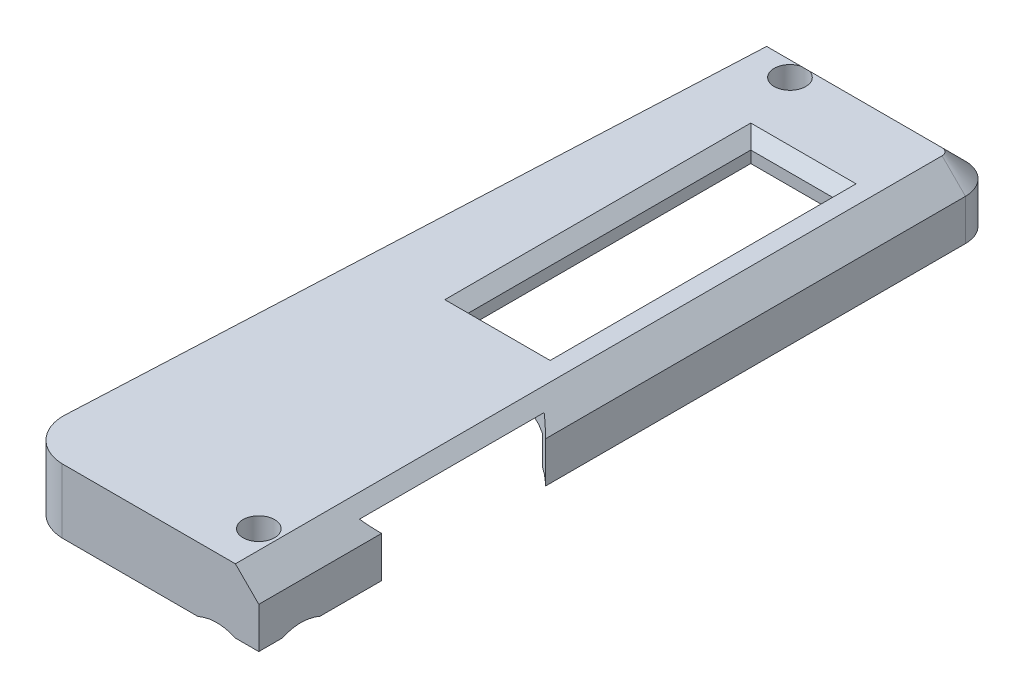
SolidWorks part; units mm, degrees
ref_plane "前视基准面" through (0, 0, 0) normal (0, 0, 1) x (1, 0, 0)
ref_plane "上视基准面" through (0, 0, 0) normal (0, 1, 0) x (1, 0, 0)
ref_plane "右视基准面" through (0, 0, 0) normal (1, 0, 0) x (0, 0, -1)
other "Configuration Table"
sketch "草图1" plane through (0, 0, 0) normal (0, 1, 0) x (1, 0, 0)
  line L0 (0, 3.3) -> (11.7, 3.3)
  line L1 (14.3, 0.7) -> (14.3, -59.7)
  line L2 (14.3, -59.7) -> (-3.3, -59.7)
  line L3 (-3.3, -59.7) -> (-3.3, 0)
  line L4 (-3.3, 0) -> (-3.3, 3.3)
  line L5 (-3.3, 3.3) -> (0, 3.3)
  circle A0 centre (0, 0) radius 1.35
  circle A1 centre (0, 0) radius 3.3 construction
  arc A2 (14.3, 0.7) -> (11.7, 3.3) centre (11.7, 0.7) ccw
  circle A3 centre (10.7, -56.1) radius 1.35
  dimension "D1" = 2.7
  dimension "D2" = 6.6
  dimension "D3" = 14.3
  dimension "D4" = 2.6
  dimension "D6" = 10.7
  dimension "D7" = 56.1
  dimension "D5" = 63
extrude "凸台-拉伸1" add sketch "草图1" along normal blind 2
sketch "草图2" plane through (0, 2, 0) normal (0, 1, 0) x (1, 0, 0)
  line L0 (-3.3, 1.1799) -> (-6.1716, -59.7)
  line L1 (-3.3, 1.1799) -> (-3.3, -59.7)
  line L2 (-6.0014, -56.0919) -> (-3.2, 3.3) construction
  line L4 (-3.3, -59.7) -> (-6.1716, -59.7)
  line L7 (-3.3, 3.3) -> (-3.3, -59.7) construction
extrude "凸台-拉伸2" add sketch "草图2" against normal up to surface (2 mm away) up to face at (6.8477, 0, 22.3123)
sketch "草图3" plane through (0, 2, 0) normal (0, 1, 0) x (1, 0, 0)
  line L0 (-3.3, 1.1799) -> (-3.2, 3.3)
  line L1 (11.7, 3.3) -> (-3.3, 3.3) construction
  line L2 (-3.2, 3.3) -> (-3.3, 3.3)
  line L3 (-3.3, 3.3) -> (-3.3, 1.1799)
  line L4 (-3.3, 1.1799) -> (-6.1716, -59.7) construction
  line L5 (-2.3, -59.7) -> (-6.1716, -59.7)
  line L6 (-6.1716, -59.7) -> (-6.0014, -56.0919)
  arc A0 (-6.0014, -56.0919) -> (-2.3, -59.7) centre (-2.4, -56.1) ccw construction
  arc A1 (-6.0014, -56.0919) -> (-2.3, -59.7) centre (-2.4, -56.1) ccw
  line M3 (11.7, 3.3) -> (-3.3, 3.3)
  line M4 (-3.3, 3.3) -> (-3.3, 1.1799)
  line M5 (-3.3, 1.1799) -> (-6.1716, -59.7)
  line M6 (-6.1716, -59.7) -> (14.3, -59.7)
extrude "切除-拉伸1" cut sketch "草图3" against normal through all and the other way through all contours L0 M4 M3 | A1 M5 M6
sketch "草图4" plane through (0, 0, 0) normal (0, -1, 0) x (1, 0, 0)
  line L21 (12.8, -0.7) -> (12.8, 58.2)
  line L22 (12.8, 58.2) -> (-2.4764, 58.2)
  line L23 (-4.5013, 56.1245) -> (-1.7691, -1.8)
  line L24 (-1.7691, -1.8) -> (11.7, -1.8)
  line L25 (12.8, -0.7) -> (12.8, 54.3245)
  line L26 (8.9245, 58.2) -> (-2.4764, 58.2)
  line L27 (-4.5013, 56.1245) -> (-1.9457, 1.9434)
  line L28 (2.0791, -1.8) -> (11.7, -1.8)
  line L33 (-6.0014, 56.0919) -> (-3.2, -3.3)
  line L34 (-3.2, -3.3) -> (11.7, -3.3)
  line L35 (14.3, -0.7) -> (14.3, 59.7)
  line L36 (14.3, 59.7) -> (-2.5, 59.7)
  line L37 (-6.0014, 56.0919) -> (-3.2, -3.3)
  line L38 (-3.2, -3.3) -> (11.7, -3.3)
  line L39 (14.3, -0.7) -> (14.3, 59.7)
  line L40 (14.3, 59.7) -> (-2.5, 59.7)
  arc A7 (11.7, -1.8) -> (12.8, -0.7) centre (11.7, -0.7) ccw
  arc A8 (-2.4764, 58.2) -> (-4.5013, 56.1245) centre (-2.4, 56.1) ccw
  arc A9 (11.7, -1.8) -> (12.8, -0.7) centre (11.7, -0.7) ccw
  arc A10 (-2.4764, 58.2) -> (-4.5013, 56.1245) centre (-2.4, 56.1) ccw
  arc A13 (11.7, -3.3) -> (14.3, -0.7) centre (11.7, -0.7) ccw
  arc A14 (-2.5, 59.7) -> (-6.0014, 56.0919) centre (-2.4, 56.1) ccw
  arc A15 (11.7, -3.3) -> (14.3, -0.7) centre (11.7, -0.7) ccw
  arc A16 (-2.5, 59.7) -> (-6.0014, 56.0919) centre (-2.4, 56.1) ccw
  circle A21 centre (10.7, 56.1) radius 2.75
  arc A22 (12.8, 54.3245) -> (8.9245, 58.2) centre (10.7, 56.1) ccw
  circle A24 centre (0, 0) radius 2.75
  arc A25 (-1.9457, 1.9434) -> (2.0791, -1.8) centre (0, 0) ccw
  dimension "D1" = 1.5
  dimension "D2" = 0
  dimension "D3" = 0.5
  dimension "D4" = 0.5
extrude "凸台-拉伸3" add sketch "草图4" along normal up to surface (3.5 mm away)
sketch "草图5" plane through (14.3, 0, 0) normal (1, 0, 0) x (0, 0, -1)
  line L0 (-59.7, -3.5) -> (0.7, -3.5) construction
  line L1 (-35.2, -3.5) -> (-49.2, -3.5)
  line L2 (-35.2, -3.5) -> (-35.2, 1)
  line L3 (-35.2, 1) -> (-49.2, 1)
  line L4 (-49.2, -3.5) -> (-49.2, 1)
  line L5 (-35.2, -3.5) -> (-49.2, 1) construction
  line L6 (-35.2, 1) -> (-49.2, -3.5) construction
  line L7 (-42.2, 0.55) -> (-42.2, -3.5) construction
  line L8 (-34.0108, 0.55) -> (-50.3892, 0.55) construction
  point P4 (-42.2, -1.25)
  dimension "D1" = 14
  dimension "D2" = 4.5
extrude "切除-拉伸2" cut sketch "草图5" against normal blind 9
sketch "草图6" plane through (0, -3.5, 0) normal (0, -1, 0) x (1, 0, 0)
  line L0 (2.1586, 33.5397) -> (2.1586, 50.8603)
  arc A0 (2.1586, 33.5397) -> (2.1586, 50.8603) centre (7.1586, 42.2) ccw
  dimension "D1" = 20
  dimension "D2" = 5
extrude "切除-拉伸3" cut sketch "草图6" against normal up to surface (4.5 mm away) up to face at (9.8, 1, 42.2)
sketch "草图7" plane through (0, 0, 0) normal (0, -1, 0) x (1, 0, 0)
  line L0 (1.3, 17.3) -> (10.6, 17.3) construction
  line L1 (12.8, 2.6) -> (1.3, 2.6) construction
  line L2 (12.8, 2.6) -> (12.8, 30.6) construction
  line L3 (12.8, 30.6) -> (1.3, 30.6) construction
  line L4 (1.3, 2.6) -> (1.3, 30.6) construction
  line L5 (12.8, 2.6) -> (1.3, 30.6) construction
  line L6 (12.8, 30.6) -> (1.3, 2.6) construction
  line L7 (1.8, 30.25) -> (10.6, 30.25) construction
  line L8 (1.8, 30.25) -> (1.8, 4.35) construction
  line L9 (1.8, 4.35) -> (10.6, 4.35) construction
  line L10 (10.6, 30.25) -> (10.6, 4.35) construction
  line L11 (1.8, 30.25) -> (10.6, 4.35) construction
  line L12 (1.8, 4.35) -> (10.6, 30.25) construction
  line L13 (6.2, 30.25) -> (6.2, 4.35) construction
  line L15 (2.7, 29.3) -> (9.7, 29.3)
  line L16 (2.7, 29.3) -> (2.7, 5.3)
  line L17 (2.7, 5.3) -> (9.7, 5.3)
  line L18 (9.7, 29.3) -> (9.7, 5.3)
  line L19 (2.7, 29.3) -> (9.7, 5.3) construction
  line L20 (2.7, 5.3) -> (9.7, 29.3) construction
  point P4 (7.05, 16.6)
  point P10 (6.2, 17.3)
  point P21 (6.2, 17.3)
  dimension "D1" = 28
  dimension "D2" = 11.5
  dimension "D3" = 0.35
  dimension "D4" = 0.5
  dimension "D5" = 8.8
  dimension "D6" = 25.9
  dimension "D7" = 24
  dimension "D8" = 7
extrude "切除-拉伸4" cut sketch "草图7" against normal through all
sketch "草图8" plane through (0, 0, 0) normal (0, -1, 0) x (1, 0, 0)
  line L0 (-2.8917, 22) -> (0.3, 22)
  line L1 (-1.9457, 1.9434) -> (-4.5013, 56.1245) construction
  line L2 (0.3, 22) -> (0.3, 18)
  line L3 (0.3, 18) -> (-2.703, 18)
  line L4 (-2.703, 18) -> (-2.8917, 22)
  line L5 (1.3, 2.6) -> (1.3, 30.6) construction
  line L7 (-2.5143, 14) -> (0.3, 14)
  line L8 (0.3, 14) -> (0.3, 10)
  line L9 (0.3, 10) -> (-2.3257, 10)
  line L10 (-2.3257, 10) -> (-2.5143, 14)
  dimension "D1" = 1
  dimension "D2" = 4
  dimension "D3" = 4
  dimension "D4" = 10
  dimension "D5" = 4
extrude "凸台-拉伸4" add sketch "草图8" along normal offset from surface (3 mm away) 0.5 up to face at (6.7611, -3.5, 31.1962)
sketch "草图9" plane through (0, 0, 0) normal (0, -1, 0) x (1, 0, 0)
  line L0 (2.75, 0) -> (2.75, 2.6)
  line L1 (12.8, 2.6) -> (1.3, 2.6) construction
  line L3 (2.75, 2.6) -> (3.3, 2.6)
  line L4 (3.3, 2.6) -> (3.3, -1.8)
  line L5 (11.7, -1.8) -> (2.0791, -1.8) construction
  line L6 (3.3, -1.8) -> (2.0791, -1.8)
  line L7 (1.3, 2.6) -> (1.3, 30.6) construction
  arc A0 (2.0791, -1.8) -> (2.75, 0) centre (0, 0) ccw
  dimension "D1" = 2
extrude "凸台-拉伸5" add sketch "草图9" along normal up to surface (3 mm away) up to face at (-1.06, -3, 12)
chamfer "倒角2" distance 1.5 angle 45 3 edges at (0.3, -3, 12) (0.3, -3, 20) (3.025, -3, 2.6)
sketch "草图10" plane through (0, 0, 0) normal (0, -1, 0) x (1, 0, 0)
  line L0 (0.3, 22) -> (0.3, 31.6)
  line L1 (0.3, 31.6) -> (-3.3445, 31.6)
  line L2 (-1.9457, 1.9434) -> (-4.5013, 56.1245) construction
  line L3 (-3.3445, 31.6) -> (-2.8917, 22)
  line L4 (-2.8917, 22) -> (0.3, 22)
  line L5 (0.3, 18) -> (0.3, 14)
  line L6 (0.3, 14) -> (-2.5143, 14)
  line L7 (-2.5143, 14) -> (-2.703, 18)
  line L8 (-2.703, 18) -> (0.3, 18)
  line L9 (12.8, 30.6) -> (1.3, 30.6) construction
  dimension "D1" = 1
extrude "凸台-拉伸6" add sketch "草图10" along normal blind 1
sketch "草图11" plane through (0, 0, 0) normal (0, -1, 0) x (1, 0, 0)
  line L0 (0.3, 31.6) -> (12.8, 31.6)
  line L1 (12.8, 33.9432) -> (12.8, -0.7) construction
  line L2 (12.8, 31.6) -> (12.8, 33.9432)
  line L3 (0.3, 31.6) -> (-3.3445, 31.6)
  line L4 (-1.9457, 1.9434) -> (-4.5013, 56.1245) construction
  line L5 (0.3, 31.6) -> (-3.3445, 31.6) construction
  line L6 (-3.3445, 31.6) -> (-3.4388, 33.6)
  line L7 (-3.4388, 33.6) -> (2.1586, 33.6)
  line L8 (2.1586, 33.5397) -> (2.1586, 50.8603) construction
  line L9 (2.1586, 33.5397) -> (2.1586, 33.6)
  arc A0 (2.1586, 33.5397) -> (14.3, 35.2) centre (7.1586, 42.2) ccw construction
  arc A1 (2.1586, 33.5397) -> (12.8, 33.9432) centre (7.1586, 42.2) ccw
  dimension "D1" = 2
extrude "凸台-拉伸7" add sketch "草图11" along normal up to surface (1 mm away) up to face at (-1.409, -1, 26.8)
sketch "草图12" plane through (0, 2, 0) normal (0, 1, 0) x (1, 0, 0)
  circle A0 centre (0, 0) radius 3
  circle A1 centre (10.7, -56.1) radius 3
  dimension "D1" = 6
  dimension "D2" = 6
chamfer "倒角3" distance 1.2 angle 45 2 edges at (12.6445, -3.5, 58.0445) (-1.8729, -3.5, -2.0136)
sketch "草图13" plane through (0, 2, 0) normal (0, 1, 0) x (1, 0, 0)
  line L1 (2.7, -29.3) -> (9.7, -29.3)
  line L2 (2.7, -29.3) -> (2.7, -30.2)
  line L3 (2.7, -30.2) -> (9.7, -30.2)
  line L4 (9.7, -29.3) -> (9.7, -30.2)
  line L5 (2.7, -29.3) -> (9.7, -30.2) construction
  line L6 (2.7, -30.2) -> (9.7, -29.3) construction
  point P4 (6.2, -29.75)
  dimension "D1" = 0.9
extrude "切除-拉伸6" cut sketch "草图13" against normal up to next and the other way through all
sketch "草图14" plane through (0, 2, 0) normal (0, 1, 0) x (1, 0, 0)
  line L0 (9.7, -29.3) -> (9.7, -5.3) construction
  line L1 (2.7, -5.3) -> (9.7, -5.3)
  line L2 (2.7, -5.3) -> (2.7, -6.05)
  line L3 (2.7, -6.05) -> (9.7, -6.05)
  line L4 (9.7, -5.3) -> (9.7, -6.05)
  line L5 (2.7, -5.3) -> (9.7, -6.05) construction
  line L6 (2.7, -6.05) -> (9.7, -5.3) construction
  point P4 (6.2, -5.675)
  dimension "D1" = 0.75
extrude "凸台-拉伸8" add sketch "草图14" against normal up to surface (2 mm away) up to face at (4.0457, 0, 7.4821)
chamfer "倒角1" distance 1 angle 45 4 edges at (9.7, 2, 18.125) (2.7, 2, 18.125) (6.2, 2, 30.2) (6.2, 2, 6.05)
sketch "草图15" plane through (0, -3, 0) normal (0, -1, 0) x (1, 0, 0)
  line L0 (-2.3257, 10) -> (-2.3257, 21)
  line L1 (-2.3257, 21) -> (0.3, 21)
  line L2 (0.3, 22) -> (0.3, 18) construction
  line L3 (0.3, 21) -> (0.3, 10)
  line L4 (0.3, 10) -> (-2.3257, 10)
  dimension "D1" = 11
extrude "切除-拉伸7" cut sketch "草图15" against normal offset from surface (2.7 mm away) 3.2 up to face at (-0.7335, -3.5, 44.3353)
sketch "草图16" plane through (0, -3, 0) normal (0, -1, 0) x (1, 0, 0)
  line L0 (2.75, -2.0833) -> (2.75, 1.1) construction
  line L1 (2.75, 0) -> (3.3, 0)
  line L2 (2.75, 0) -> (2.75, 2.6)
  line L3 (2.75, 2.6) -> (3.3, 2.6)
  line L4 (3.3, 0) -> (3.3, 2.6)
  line L5 (2.75, 0) -> (3.3, 2.6) construction
  line L6 (2.75, 2.6) -> (3.3, 0) construction
  point P4 (3.025, 1.3)
extrude "切除-拉伸8" cut sketch "草图16" against normal up to surface (3 mm away)
sketch "草图17" plane through (0, -3.5, 0) normal (0, -1, 0) x (1, 0, 0)
  line L0 (12.8, 2.6) -> (12.8, 30.6) construction
  line L1 (12.8, 6.5) -> (13.5, 6.5)
  line L2 (12.8, 6.5) -> (12.8, 2.5)
  line L3 (12.8, 2.5) -> (13.5, 2.5)
  line L4 (13.5, 6.5) -> (13.5, 2.5)
  line L5 (12.8, 6.5) -> (13.5, 2.5) construction
  line L6 (12.8, 2.5) -> (13.5, 6.5) construction
  point P4 (13.15, 4.5)
  dimension "D1" = 0.7
  dimension "D2" = 2.5
  dimension "D3" = 4
extrude "切除-拉伸9" cut sketch "草图17" against normal blind 2
sketch "草图18" plane through (0, 0, 0) normal (0, -1, 0) x (1, 0, 0)
  line L0 (-2.4764, 58.2) -> (7.3545, 58.2) construction
  line L1 (0.3, 22) -> (-1.7, 22)
  line L2 (0.3, 22) -> (0.3, 58.2)
  line L3 (0.3, 58.2) -> (-1.7, 58.2)
  line L4 (-1.7, 22) -> (-1.7, 58.2)
  line L5 (0.3, 22) -> (-1.7, 58.2) construction
  line L6 (0.3, 58.2) -> (-1.7, 22) construction
  point P4 (-0.7, 40.1)
  dimension "D1" = 2
extrude "凸台-拉伸9" add sketch "草图18" along normal blind 2
sketch "草图19" plane through (0, 0, 0) normal (0, -1, 0) x (1, 0, 0)
  line L0 (9.3574, 53.7) -> (0.3, 53.7)
  line L1 (0.3, 33.6) -> (0.3, 58.2) construction
  line L2 (0.3, 53.7) -> (0.3, 51.7)
  line L3 (0.3, 22) -> (0.3, 58.2) construction
  line L5 (12.8, 50.4568) -> (12.8, 54.3245)
  line L6 (0.3, 51.7) -> (4.0361, 51.7)
  line L7 (-2.4764, 58.2) -> (7.3545, 58.2) construction
  arc A0 (14.3, 49.2) -> (2.1586, 50.8603) centre (7.1586, 42.2) ccw construction
  arc A1 (12.8, 50.4568) -> (4.0361, 51.7) centre (7.1586, 42.2) ccw
  arc A2 (9.3574, 53.7) -> (12.8, 54.3245) centre (10.7, 56.1) ccw
  dimension "D1" = 2
  dimension "D2" = 4.5
extrude "凸台-拉伸10" add sketch "草图19" along normal up to surface (2 mm away) up to face at (-0.6, -2, 36.48)
sketch "草图20" plane through (0, 0, 0) normal (0, -1, 0) x (1, 0, 0)
  line L0 (-2.0143, 3.3978) -> (-4.5013, 56.1245) construction
  line L1 (0.3, 51.7) -> (-4.3869, 51.7)
  line L2 (0.3, 51.7) -> (0.3, 53.7)
  line L3 (0.3, 53.7) -> (-4.3869, 53.7)
  line L4 (-4.3869, 51.7) -> (-4.3869, 53.7)
  line L5 (0.3, 51.7) -> (-4.3869, 53.7) construction
  line L6 (0.3, 53.7) -> (-4.3869, 51.7) construction
  point P4 (-2.0434, 52.7)
extrude "凸台-拉伸11" add sketch "草图20" along normal up to surface (2 mm away) up to face at (3.3501, -2, 45.3078)
sketch "草图21" plane through (0, -1, 0) normal (0, -1, 0) x (1, 0, 0)
  line L0 (-2.0143, 3.3978) -> (-4.5013, 56.1245) construction
  line L1 (-1.7, 33.6) -> (-3.4388, 33.6)
  line L2 (-1.7, 33.6) -> (-1.7, 31.6)
  line L3 (-1.7, 31.6) -> (-3.4388, 31.6)
  line L4 (-3.4388, 33.6) -> (-3.4388, 31.6)
  line L5 (-1.7, 33.6) -> (-3.4388, 31.6) construction
  line L6 (-1.7, 31.6) -> (-3.4388, 33.6) construction
  line L7 (-3.4388, 33.6) -> (-2.8917, 22) construction
  point P4 (-2.5694, 32.6)
  dimension "D1" = 2
extrude "凸台-拉伸12" add sketch "草图21" along normal up to surface (1 mm away) up to face at (1.6514, -2, 47.279)
sketch "草图22" plane through (0, 0, 22) normal (0, 0, -1) x (-1, 0, 0)
  line L3 (0.2, -2) -> (-0.3, -1.5)
  line L4 (-0.3, -1.5) -> (-0.3, -2)
  line L5 (-0.3, -2) -> (0.2, -2)
  line L6 (0.2, -2) -> (-0.3, -1.5)
  line L7 (-0.3, -1.5) -> (-0.3, -2)
  line L8 (-0.3, -2) -> (0.2, -2)
  dimension "D1" = 0
extrude "切除-拉伸10" cut sketch "草图22" against normal up to surface (29.7 mm away) up to face at (2.168, -1, 51.7)
chamfer "倒角4" distance 2 angle 45 3 edges at (4.25, 2, -3.3) (13.5385, 2, -2.5385) (14.3, 2, 29.5)
